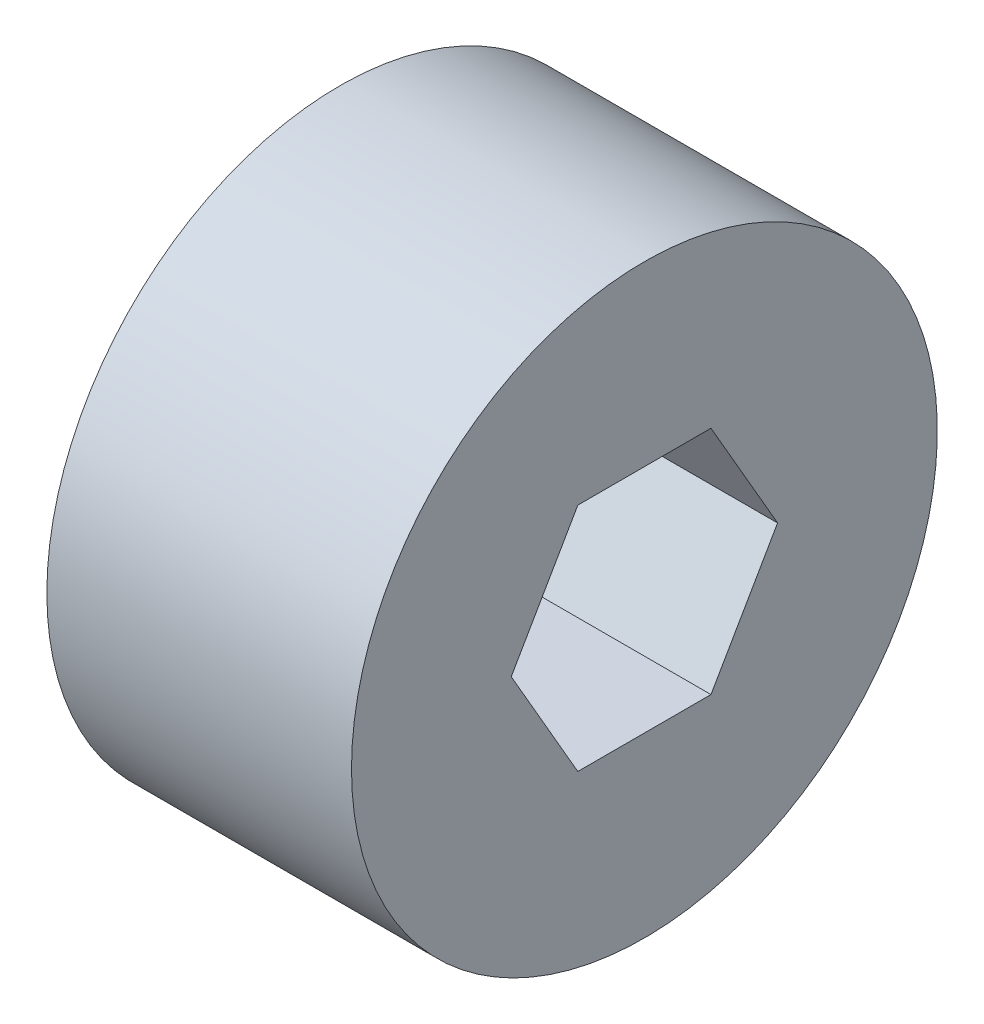
SolidWorks part; units mm, degrees
material "PET"
ref_plane "Front" through (0, 0, 0) normal (0, 0, 1) x (1, 0, 0)
ref_plane "Top" through (0, 0, 0) normal (0, 1, 0) x (1, 0, 0)
ref_plane "Right" through (0, 0, 0) normal (1, 0, 0) x (0, 0, -1)
sketch "Sketch1" plane through (0, 0, 0) normal (1, 0, 0) x (0, 0, -1)
  line L1 (2.8868, 0) -> (1.4434, 2.5)
  line L2 (1.4434, 2.5) -> (-1.4434, 2.5)
  line L3 (-1.4434, 2.5) -> (-2.8868, 0)
  line L4 (-2.8868, 0) -> (-1.4434, -2.5)
  line L5 (-1.4434, -2.5) -> (1.4434, -2.5)
  line L6 (1.4434, -2.5) -> (2.8868, 0)
  circle A0 centre (0, 0) radius 6.35
  circle A1 centre (0, 0) radius 2.5 construction
  dimension "D1" = 12.7
  dimension "D2" = 5
extrude "Boss-Extrude1" add sketch "Sketch1" along normal blind 6.604
ref_axis "Axis1" through (6.604, 0, 0) along (-1, 0, 0)
